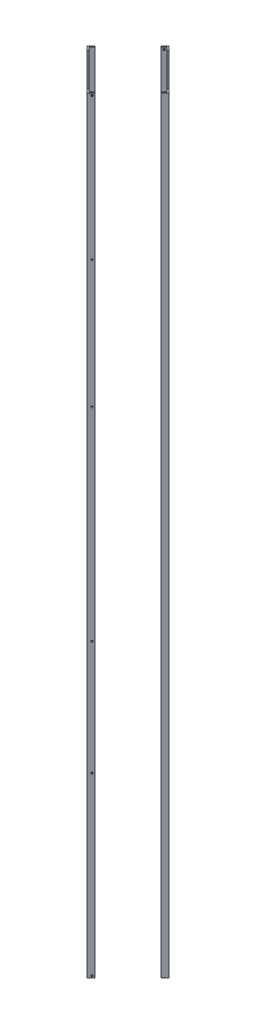
SolidWorks part; units mm, degrees
material "6061-T6 (SS)"
ref_plane "Front Plane" through (0, 0, 0) normal (0, 0, 1) x (1, 0, 0)
ref_plane "Top Plane" through (0, 0, 0) normal (0, 1, 0) x (1, 0, 0)
ref_plane "Right Plane" through (0, 0, 0) normal (1, 0, 0) x (0, 0, -1)
sketch "Sketch2" plane through (0, 0, 0) normal (0, 1, 0) x (1, 0, 0)
  line L0 (0, 94.7743) -> (-8.9803, 85.794)
  line L1 (-8.9803, 85.794) -> (-6.7352, 83.549)
  line L2 (-6.7352, 83.549) -> (0, 90.2842)
  line L3 (0, 90.2842) -> (6.7352, 83.549)
  line L4 (6.7352, 83.549) -> (8.9803, 85.794)
  line L5 (8.9803, 85.794) -> (0, 94.7743)
  line L6 (0, 0) -> (0, 186.644) construction
  line L7 (94.7417, 0.0326) -> (85.7614, 9.0128)
  line L8 (85.7614, 9.0128) -> (83.5164, 6.7678)
  line L9 (83.5164, 6.7678) -> (90.2516, 0.0326)
  line L10 (90.2516, 0.0326) -> (83.5164, -6.7026)
  line L11 (83.5164, -6.7026) -> (85.7614, -8.9477)
  line L12 (85.7614, -8.9477) -> (94.7417, 0.0326)
  line L13 (0, -94.7091) -> (8.9803, -85.7289)
  line L14 (8.9803, -85.7289) -> (6.7352, -83.4838)
  line L15 (6.7352, -83.4838) -> (0, -90.219)
  line L16 (0, -90.219) -> (-6.7352, -83.4838)
  line L17 (-6.7352, -83.4838) -> (-8.9803, -85.7289)
  line L18 (-8.9803, -85.7289) -> (0, -94.7091)
  line L19 (-94.7417, 0.0326) -> (-85.7614, -8.9477)
  line L20 (-85.7614, -8.9477) -> (-83.5164, -6.7026)
  line L21 (-83.5164, -6.7026) -> (-90.2516, 0.0326)
  line L22 (-90.2516, 0.0326) -> (-83.5164, 6.7678)
  line L23 (-83.5164, 6.7678) -> (-85.7614, 9.0128)
  line L24 (-85.7614, 9.0128) -> (-94.7417, 0.0326)
  point P1 (-3.3676, 86.9166)
  point P31 (0, 0.0326)
  dimension "D1" = 127.635
  dimension "D2" = 12.7
  dimension "D3" = 12.7
  dimension "D4" = 3.175
  dimension "D5" = 3.175
  dimension "D7" = 127.635
  dimension "D6" = 4
extrude "Boss-Extrude1" add sketch "Sketch2" along normal blind 1778
sketch "Sketch3" plane through (0, 0, 0) normal (0, -1, 0) x (1, 0, 0)
  circle A0 centre (0, 0) radius 94.7417
sketch "Sketch4" plane through (-47.3546, 0, 47.3546) normal (-0.7071, 0, 0.7071) x (0.7071, 0, 0.7071)
  line L0 (-54.3155, 0) -> (-54.3155, 4.7625)
  line L1 (-54.3155, 1778) -> (-54.3155, 0) construction
  line L2 (-54.3155, 4.7625) -> (-67.0155, 4.7625)
  line L3 (-67.0155, 1778) -> (-67.0155, 0) construction
  line L4 (-67.0155, 0) -> (-54.3155, 0) construction
  circle A0 centre (-59.078, 4.7625) radius 2.0066
  dimension "D2" = 4.0132
  dimension "D3" = 7.9375
  dimension "D4" = 4.7625
  dimension "D1" = 4.7625
extrude "Cut-Extrude1" cut sketch "Sketch4" against normal up to next (3.175 mm away) contours L2 A0 | L2 A0 region at (-89.129, 3.9109, 5.5801) region at (-89.129, 5.6141, 5.5801)
sketch "Sketch5" plane through (-47.3871, 0, -47.3871) normal (-0.7071, 0, -0.7071) x (-0.7071, 0, 0.7071)
  line L0 (-54.3155, 1778) -> (-54.3155, 0) construction
  line L1 (-67.0155, 0) -> (-54.3155, 0)
  line L2 (-67.0155, 0) -> (-67.0155, 4.7625)
  line L3 (-67.0155, 4.7625) -> (-54.3155, 4.7625)
  line L4 (-54.3155, 0) -> (-54.3155, 4.7625)
  line L5 (-67.0155, 1778) -> (-67.0155, 0) construction
  circle A0 centre (-59.078, 4.7625) radius 2.0066
  dimension "D2" = 4.0132
  dimension "D4" = 4.7625
  dimension "D1" = 4.7625
  dimension "D3" = 7.9375
extrude "Cut-Extrude2" cut sketch "Sketch5" against normal up to next (3.175 mm away) contours L3 A0 | L3 A0 region at (-5.6127, 5.6141, -89.1616) region at (-5.6127, 3.9109, -89.1616)
sketch "Sketch6" plane through (47.3871, 0, -47.3871) normal (0.7071, 0, -0.7071) x (-0.7071, 0, -0.7071)
  line L0 (-54.2695, 1778) -> (-54.2695, 0) construction
  line L1 (-66.9695, 0) -> (-54.2695, 0)
  line L2 (-66.9695, 0) -> (-66.9695, 4.7625)
  line L3 (-66.9695, 4.7625) -> (-54.2695, 4.7625)
  line L4 (-54.2695, 0) -> (-54.2695, 4.7625)
  line L5 (-66.9695, 1778) -> (-66.9695, 0) construction
  circle A0 centre (-59.032, 4.7625) radius 2.0066
  dimension "D2" = 4.0132
  dimension "D4" = 4.7625
  dimension "D1" = 4.7625
  dimension "D3" = 7.9375
extrude "Cut-Extrude3" cut sketch "Sketch6" against normal up to next (3.175 mm away) contours L3 A0 | L3 A0 region at (89.129, 5.6141, -5.6452) region at (89.129, 3.9109, -5.6452)
sketch "Sketch7" plane through (47.3546, 0, 47.3546) normal (0.7071, 0, 0.7071) x (0.7071, 0, -0.7071)
  line L0 (-54.2695, 1778) -> (-54.2695, 0) construction
  line L1 (-66.9695, 0) -> (-54.2695, 0)
  line L2 (-66.9695, 0) -> (-66.9695, 4.7625)
  line L3 (-66.9695, 4.7625) -> (-54.2695, 4.7625)
  line L4 (-54.2695, 0) -> (-54.2695, 4.7625)
  line L5 (-66.9695, 1778) -> (-66.9695, 0) construction
  circle A0 centre (-59.032, 4.7625) radius 2.0066
  dimension "D2" = 4.0132
  dimension "D3" = 7.9375
  dimension "D4" = 4.7625
  dimension "D1" = 4.7625
extrude "Cut-Extrude4" cut sketch "Sketch7" against normal up to next (3.175 mm away) contours L3 A0 | L3 A0 region at (5.6127, 5.6141, 89.0965) region at (5.6127, 3.9109, 89.0965)
pattern_linear "LPattern1" count 2 spacing 407.035 along (0, 1, 0) of "Cut-Extrude4", "Cut-Extrude3", "Cut-Extrude1", "Cut-Extrude2"
pattern_linear "LPattern2" count 2 spacing 671.83 along (0, 1, 0) of "Cut-Extrude1", "Cut-Extrude2", "Cut-Extrude3", "Cut-Extrude4"
pattern_linear "LPattern3" count 2 spacing 1143 along (0, 1, 0) of "Cut-Extrude1", "Cut-Extrude2", "Cut-Extrude3", "Cut-Extrude4"
pattern_linear "LPattern4" count 2 spacing 1438.275 along (0, 1, 0) of "Cut-Extrude1", "Cut-Extrude2", "Cut-Extrude3", "Cut-Extrude4"
pattern_linear "LPattern5" count 2 spacing 1768.4775 along (0, 1, 0) of "Cut-Extrude1", "Cut-Extrude2", "Cut-Extrude3", "Cut-Extrude4"
